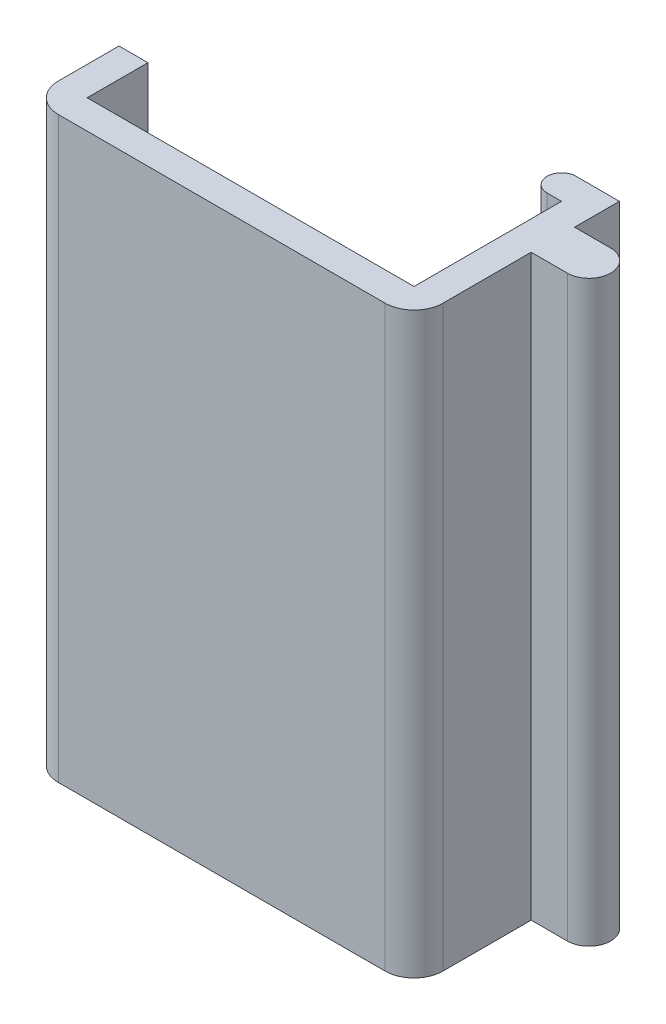
SolidWorks part; units mm, degrees
ref_plane "Alzado" through (0, 0, 0) normal (0, 0, 1) x (1, 0, 0)
ref_plane "Planta" through (0, 0, 0) normal (0, 1, 0) x (1, 0, 0)
ref_plane "Vista lateral" through (0, 0, 0) normal (1, 0, 0) x (0, 0, -1)
sketch "Croquis3" plane through (0, 0, 0) normal (0, 1, 0) x (1, 0, 0)
  line L0 (-2.7263, 0) -> (-4.0174, 0)
  line L1 (-4.0174, 0) -> (-4.0174, -3.1)
  line L2 (-4.0174, -3.1) -> (9.2826, -3.1)
  line L3 (9.2826, -3.1) -> (9.2826, 4)
  line L4 (9.2826, 4) -> (7.2826, 4)
  line L5 (7.2826, 4) -> (7.2826, 3)
  line L6 (7.2826, 3) -> (8.2826, 3)
  line L7 (8.2826, 3) -> (8.2826, -2.1)
  line L8 (8.2826, -2.1) -> (-3.0174, -2.1)
  line L9 (-3.0174, -2.1) -> (-3.0174, -1)
  line L10 (-3.0174, -1) -> (-2.7263, -1)
  line L11 (-2.7263, -1) -> (-2.7263, 0)
  point P3 (2.6326, -3.1)
  dimension "D1" = 1
  dimension "D2" = 1
  dimension "D3" = 1
  dimension "D4" = 13.3
  dimension "D5" = 1
  dimension "D8" = 1
  dimension "D10" = 5.1
extrude "Saliente-Extruir1" add sketch "Croquis3" along normal blind 20
fillet "Redondeo1" 2 edges at (7.2826, 10, -3) (7.2826, 10, -4) type full round first side face at (7.7826, 10, -3) second side face at (8.2826, 10, -4) middle face at (7.2826, 10, -3.5)
fillet "Redondeo3" radius 1 1 edges at (-4.0174, 10, 3.1) type face fillet first side face at (-4.0174, 10, 1.55) second side face at (2.6326, 10, 3.1)
fillet "Redondeo4" radius 1 1 edges at (9.2826, 10, 3.1) type face fillet first side face at (3.1326, 10, 3.1) second side face at (9.2826, 10, -0.45)
sketch "Croquis6" plane through (0, 20, 0) normal (0, 1, 0) x (1, 0, 0)
  line L1 (-3.0174, -1) -> (-2.4982, -1)
  line L2 (-3.0174, -1) -> (-3.0174, 0.1341)
  line L3 (-3.0174, 0.1341) -> (-2.4982, 0.1341)
  line L4 (-2.4982, -1) -> (-2.4982, 0.1341)
extrude "Cortar-Extruir2" cut sketch "Croquis6" against normal blind 31
sketch "Croquis7" plane through (9.2826, 0, 0) normal (1, 0, 0) x (0, 0, -1)
  line L0 (-2.1, 20) -> (4, 20) construction
  line L1 (0.95, 20) -> (2.45, 20)
  line L2 (0.95, 20) -> (0.95, 0)
  line L3 (0.95, 0) -> (2.45, 0)
  line L4 (2.45, 20) -> (2.45, 0)
  line L5 (18.7344, 0) -> (-18.7344, 0) construction
  dimension "D1" = 1.5
extrude "Saliente-Extruir2" add sketch "Croquis7" along normal blind 2
fillet "Redondeo5" 2 edges at (11.2826, 10, -2.45) (11.2826, 10, -0.95) type full round first side face at (10.2826, 10, -2.45) second side face at (10.2826, 10, -0.95) middle face at (11.2826, 10, -1.7)
